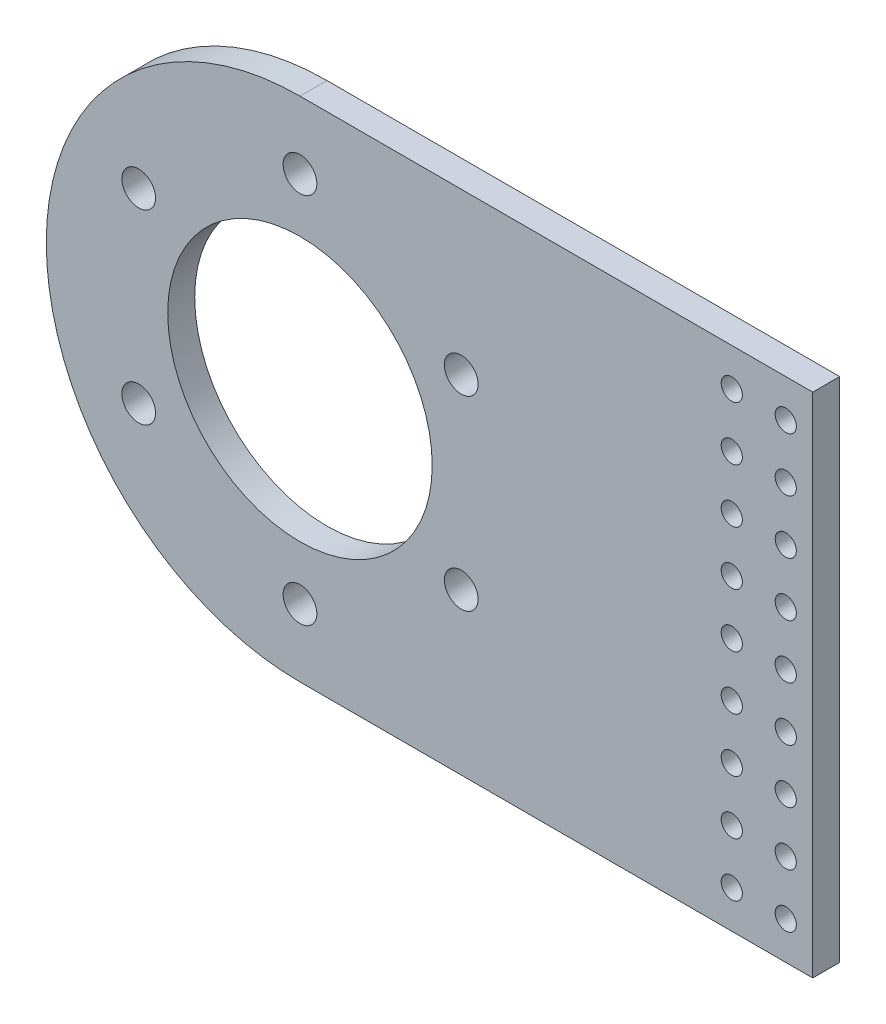
SolidWorks part; units mm, degrees
ref_plane "Front Plane" through (0, 0, 0) normal (1, 0, 0) x (0, 1, 0)
ref_plane "Top Plane" through (0, 0, 0) normal (0, 0, 1) x (0, 1, 0)
ref_plane "Right Plane" through (0, 0, 0) normal (0, 1, 0) x (-1, 0, 0)
sketch "Sketch1" plane through (0, 0, 0) normal (0, 0, 1) x (0, 1, 0)
  line L0 (-59.69, 0) -> (-59.69, -120.65)
  line L1 (-59.69, -120.65) -> (59.69, -120.65)
  line L2 (59.69, -120.65) -> (59.69, 0)
  circle A0 centre (0, 0) radius 25.4 construction
  circle A1 centre (0, 0) radius 27.94 construction
  circle A2 centre (0, 0) radius 43.815 construction
  circle A3 centre (-43.815, 0) radius 15.875 construction
  circle A4 centre (-21.9075, 37.9449) radius 15.875 construction
  circle A5 centre (21.9075, 37.9449) radius 15.875 construction
  circle A6 centre (43.815, 0) radius 15.875 construction
  circle A7 centre (21.9075, -37.9449) radius 15.875 construction
  circle A8 centre (-21.9075, -37.9449) radius 15.875 construction
  arc A9 (59.69, 0) -> (-59.69, 0) centre (0, 0) ccw
  circle A10 centre (0, 0) radius 31.115
  point P5 (-43.815, 0)
  point P8 (-21.9075, 37.9449)
  point P13 (21.9075, 37.9449)
  point P16 (43.815, 0)
  point P19 (21.9075, -37.9449)
  point P22 (-21.9075, -37.9449)
  point P25 (0, 0)
  dimension "D1" = 50.8
  dimension "D2" = 2.54
  dimension "D3" = 15.875
  dimension "D4" = 31.75
  dimension "D5" = 6
  dimension "D6" = 3.175
  dimension "D7" = 120.65
extrude "Boss-Extrude1" add sketch "Sketch1" along normal blind 6.35
sketch "Sketch2" plane through (0, 0, 6.35) normal (0, 0, 1) x (1, 0, 0)
  line L0 (120.65, -59.69) -> (120.65, 59.69) construction
  point P0 (114.3, -50.8)
  point P8 (101.6, -50.8)
  point P9 (101.6, -38.1)
  point P10 (101.6, -25.4)
  point P11 (101.6, -12.7)
  point P12 (101.6, 0)
  point P13 (101.6, 12.7)
  point P14 (101.6, 25.4)
  point P15 (101.6, 38.1)
  point P16 (101.6, 50.8)
  point P17 (114.3, -38.1)
  point P18 (114.3, -25.4)
  point P19 (114.3, -12.7)
  point P20 (114.3, 0)
  point P21 (114.3, 12.7)
  point P22 (114.3, 25.4)
  point P23 (114.3, 38.1)
  point P24 (114.3, 50.8)
  point P28 (0, 0)
  dimension "D1" = 6.35
  dimension "D2" = 2
  dimension "D5" = 12.7
  dimension "D6" = 12.7
  dimension "D4" = 9
hole_wizard "#9 (0.196) Diameter Hole1" positions "Sketch2" profile "Sketch3" hole size "#9" standard "ANSI Inch" end condition through all
sketch "Sketch3" plane through (114.3, -50.8, 6.35) normal (1, 0, 0) x (0, -1, 0)
  line L0 (0, 0) -> (0, 6.35)
  line L1 (0, 6.35) -> (2.4892, 6.35)
  line L2 (2.4892, 6.35) -> (2.4892, 0)
  line L5 (2.4892, 0) -> (0, 0)
  line L11 (0, -6.35) -> (0, 107.95) construction
  dimension "Thru Hole Dia." = 4.9784
  dimension "Thru Hole Depth" = 6.35
sketch "Sketch4" plane through (0, 0, 6.35) normal (0, 0, 1) x (1, 0, 0)
  point P0 (37.9449, 21.9075)
  point P2 (37.9449, -21.9075)
  point P4 (0, -43.815)
  point P6 (-37.9449, -21.9075)
  point P8 (-37.9449, 21.9075)
  point P10 (0, 43.815)
hole_wizard "5/16 (0.3125) Diameter Hole1" positions "Sketch4" profile "Sketch5" hole size "5/16" standard "ANSI Inch" end condition through all
sketch "Sketch5" plane through (37.9449, 21.9075, 6.35) normal (1, 0, 0) x (0, -1, 0)
  line L0 (0, 0) -> (0, 6.35)
  line L1 (0, 6.35) -> (3.9688, 6.35)
  line L2 (3.9688, 6.35) -> (3.9688, 0)
  line L5 (3.9688, 0) -> (0, 0)
  line L11 (0, -6.35) -> (0, 107.95) construction
  dimension "Thru Hole Dia." = 7.9375
  dimension "Thru Hole Depth" = 6.35
